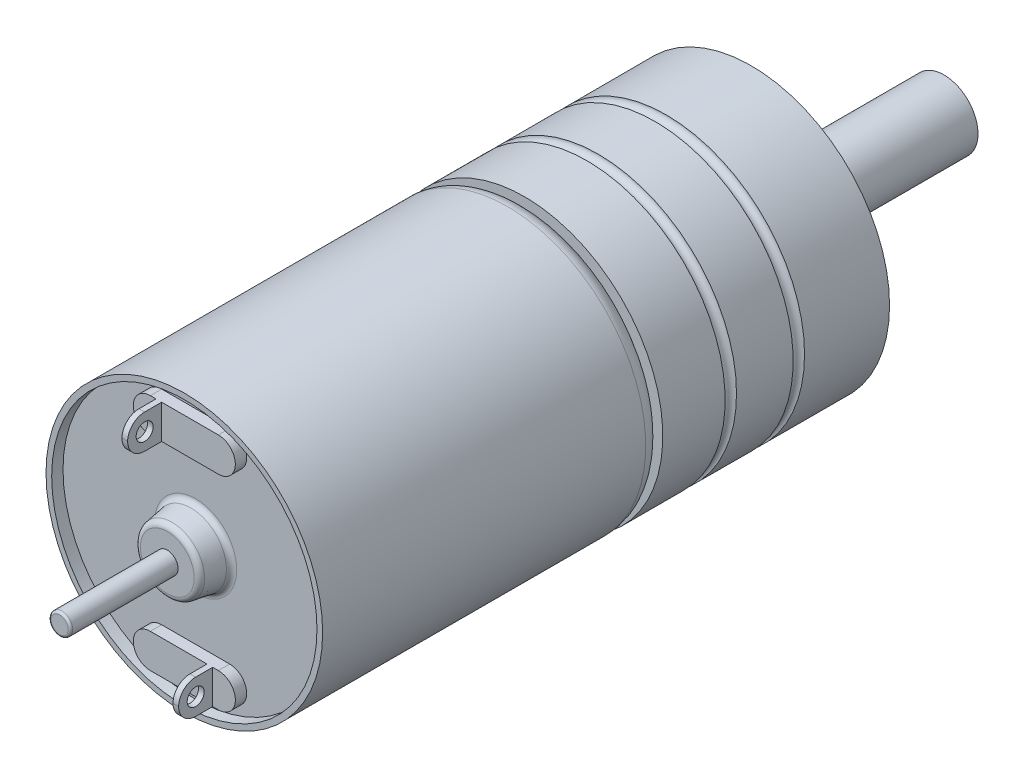
SolidWorks part; units mm, degrees
ref_plane "前视基准面" through (0, 0, 0) normal (0, 0, 1) x (1, 0, 0)
ref_plane "上视基准面" through (0, 0, 0) normal (0, 1, 0) x (1, 0, 0)
ref_plane "右视基准面" through (0, 0, 0) normal (1, 0, 0) x (0, 0, -1)
sketch "草图1" plane through (0, 0, 0) normal (0, 0, 1) x (1, 0, 0)
  circle A0 centre (0, 0) radius 12.2
  dimension "D1" = 24.4
extrude "凸台-拉伸1" add sketch "草图1" along normal blind 50
sketch "草图14" plane through (0, 0, 50) normal (0, 0, 1) x (1, 0, 0)
  circle A0 centre (0, 0) radius 11.7
  circle A1 centre (0, 0) radius 12.2 construction
  dimension "D1" = 0.5
extrude "切除-拉伸4" cut sketch "草图14" against normal blind 1
sketch "草图15" plane through (0, 0, 0) normal (0, 1, 0) x (1, 0, 0)
  line L0 (0, -49) -> (0, -51.5)
  line L1 (-11.7, -49) -> (11.7, -49) construction
  line L2 (0, -51.5) -> (-2.8, -51.5)
  line L3 (-2.8, -51.5) -> (-3.2, -49)
  line L4 (-3.2, -49) -> (0, -49)
  dimension "D1" = 2.5
  dimension "D2" = 2.8
  dimension "D3" = 3.2
revolve "旋转1" add sketch "草图15" angle 360 about L0
fillet "圆角3" radius 0.5 2 edges at (-2.8, 0, 51.5) (3.2, 0, 49)
sketch "草图16" plane through (0, 0, 51.5) normal (0, 0, 1) x (1, 0, 0)
  circle A0 centre (0, 0) radius 0.95
  dimension "D1" = 1.9
extrude "凸台-拉伸7" add sketch "草图16" along normal blind 9.5
fillet "圆角4" radius 0.2 1 edges at (0.95, 0, 61)
sketch "草图4" plane through (0, 0, 0) normal (0, 0, -1) x (-1, 0, 0)
  circle A0 centre (0, 0) radius 4.5
  dimension "D1" = 9
extrude "凸台-拉伸3" add sketch "草图4" along normal blind 2.5
sketch "草图5" plane through (0, 0, -2.5) normal (0, 0, -1) x (-1, 0, 0)
  circle A0 centre (0, 0) radius 3
  dimension "D1" = 6
extrude "凸台-拉伸4" add sketch "草图5" along normal blind 14.5
sketch "草图7" plane through (0, 0, -17) normal (0, 0, -1) x (-1, 0, 0)
  line L0 (-1.6583, -2.5) -> (1.6583, -2.5)
  circle A0 centre (0, 0) radius 3 construction
  circle A2 centre (0, 0) radius 3
  circle A3 centre (0, 0) radius 3
  circle M3 centre (0, 0) radius 3
  dimension "D1" = 2.5
  dimension "D2" = 0
extrude "切除-拉伸1" cut sketch "草图7" against normal blind 12 contours L0 M3 region at (0, -2.7015, -17)
sketch "草图8" plane through (0, 0, 0) normal (0, 0, -1) x (-1, 0, 0)
  circle A0 centre (0, 0) radius 9.5 construction
  circle A1 centre (0, 9.5) radius 1.25
  circle A2 centre (9.5, 0) radius 1.25
  circle A3 centre (0, -9.5) radius 1.25
  circle A4 centre (-9.5, 0) radius 1.25
  point P14 (0, 0)
  dimension "D1" = 19
  dimension "D2" = 2.5
  dimension "D3" = 4
extrude "切除-拉伸2" cut sketch "草图8" against normal blind 4
sketch "草图11" plane through (0, 0, 49) normal (0, 0, 1) x (1, 0, 0)
  line L0 (-3, 9) -> (3, 9) construction
  line L1 (-3, 10.5) -> (3, 10.5)
  line L2 (-3, 7.5) -> (3, 7.5)
  line L3 (0, 9) -> (0, 0) construction
  line L4 (0, 0) -> (17.2532, 0) construction
  line L5 (-3, -9) -> (3, -9) construction
  line L6 (-3, -10.5) -> (3, -10.5)
  line L7 (-3, -7.5) -> (3, -7.5)
  arc A0 (-3, 10.5) -> (-3, 7.5) centre (-3, 9) ccw
  arc A1 (3, 7.5) -> (3, 10.5) centre (3, 9) ccw
  arc A2 (-3, -10.5) -> (-3, -7.5) centre (-3, -9) cw
  arc A3 (3, -7.5) -> (3, -10.5) centre (3, -9) cw
  point P2 (0, 9)
  point P13 (0, -9)
  dimension "D2" = 1.5
  dimension "D1" = 6
  dimension "D3" = 9
extrude "凸台-拉伸5" add sketch "草图11" along normal blind 1
sketch "草图12" plane through (0, 0, 50) normal (0, 0, 1) x (1, 0, 0)
  line L0 (3, 10.5) -> (-3, 10.5) construction
  line L1 (-2.5, 10.5) -> (-2, 10.5)
  line L2 (-2.5, 10.5) -> (-2.5, 7.5)
  line L3 (-2.5, 7.5) -> (-2, 7.5)
  line L4 (-2, 10.5) -> (-2, 7.5)
  line L6 (3, -7.5) -> (-3, -7.5) construction
  line L7 (2, -7.5) -> (2.5, -7.5)
  line L8 (2, -7.5) -> (2, -10.5)
  line L9 (2, -10.5) -> (2.5, -10.5)
  line L10 (2.5, -7.5) -> (2.5, -10.5)
  line L12 (-3, 7.5) -> (3, 7.5) construction
  line L13 (-3, -10.5) -> (3, -10.5) construction
  dimension "D1" = 2
  dimension "D2" = 2
  dimension "D3" = 0.5
extrude "凸台-拉伸6" add sketch "草图12" along normal blind 3
fillet "圆角2" radius 1.5 4 edges at (-2.25, 7.5, 53) (-2.25, 10.5, 53) (2.25, -10.5, 53) (2.25, -7.5, 53)
sketch "草图13" plane through (-2, 0, 0) normal (1, 0, 0) x (0, 0, -1)
  circle A0 centre (-51.5, 9) radius 0.75
  circle A1 centre (-51.5, -9) radius 0.75
  dimension "D1" = 1.5
extrude "切除-拉伸3" cut sketch "草图13" against normal through all both and the other way through all
sketch "草图17" plane through (0, 0, 0) normal (0, 1, 0) x (1, 0, 0)
  line L0 (-12.2, 0) -> (-12.2, -50) construction
  line L1 (-10.7, -20) -> (-12.2, -20)
  line L2 (-12.2, -20) -> (-12.2, -21.5)
  line L3 (0, 0) -> (0, -61) construction
  line L4 (-0.75, -61) -> (0.75, -61) construction
  circle A0 centre (-12.2, -8) radius 0.5
  circle A1 centre (-12.2, -14) radius 0.5
  arc A2 (-10.7, -20) -> (-12.2, -21.5) centre (-10.7, -21.5) ccw
  dimension "D3" = 1
  dimension "D4" = 3
  dimension "D1" = 8
  dimension "D2" = 6
  dimension "D5" = 6
revolve "切除-旋转1" cut sketch "草图17" angle 360 about L3
chamfer "倒角1" [suppressed] distance 0.5 angle 45
